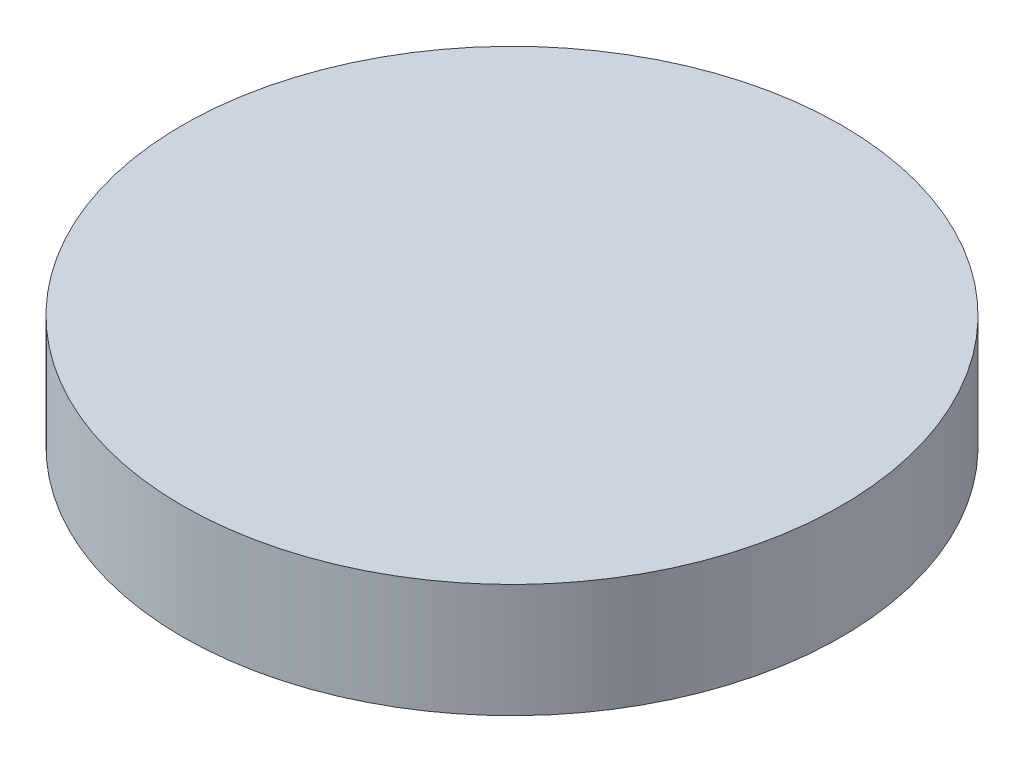
SolidWorks part; units mm, degrees
ref_plane "Front Plane" through (0, 0, 0) normal (0, 0, 1) x (1, 0, 0)
ref_plane "Top Plane" through (0, 0, 0) normal (0, 1, 0) x (1, 0, 0)
ref_plane "Right Plane" through (0, 0, 0) normal (1, 0, 0) x (0, 0, -1)
sketch "Sketch1" plane through (0, 0, 0) normal (0, 1, 0) x (1, 0, 0)
  circle A0 centre (0, 0) radius 36.83
  dimension "D1" = 73.66
extrude "Boss-Extrude1" add sketch "Sketch1" along normal blind 12.7
ref_axis "Axis1" through (0, -1.27, 0) along (0, 1, 0)
